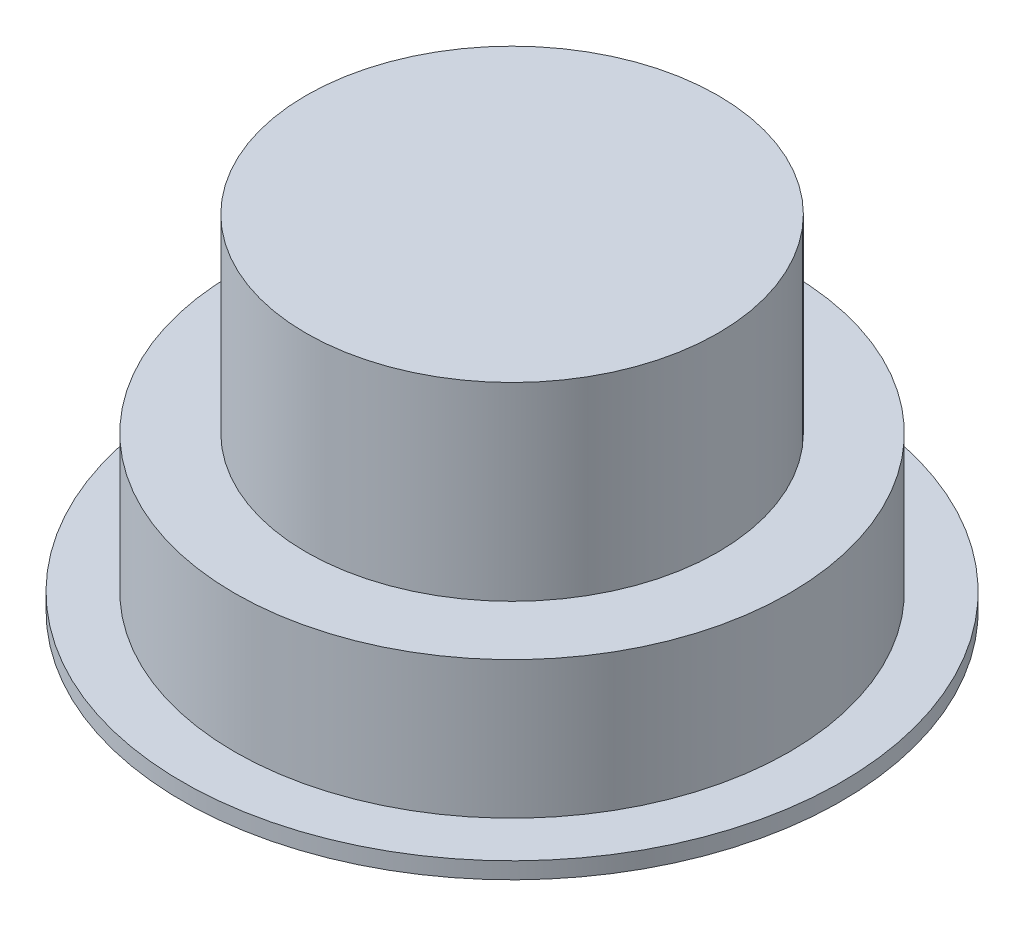
SolidWorks part; units mm, degrees
ref_plane "Plan de face" through (0, 0, 0) normal (0, 0, 1) x (1, 0, 0)
ref_plane "Plan de dessus" through (0, 0, 0) normal (0, 1, 0) x (1, 0, 0)
ref_plane "Plan de droite" through (0, 0, 0) normal (1, 0, 0) x (0, 0, -1)
sketch "Esquisse1" plane through (0, 0, 0) normal (0, 1, 0) x (1, 0, 0)
  circle A0 centre (0, 0) radius 7.5
  dimension "D1" = 15
extrude "Boss.-Extru.1" add sketch "Esquisse1" along normal blind 10.5
sketch "Esquisse2" plane through (0, 0, 0) normal (0, -1, 0) x (1, 0, 0)
  circle A0 centre (0, 0) radius 10.1
  dimension "D1" = 20.2
extrude "Boss.-Extru.2" add sketch "Esquisse2" along normal blind 2 and the other way blind 3.6
sketch "Esquisse3" plane through (0, -2, 0) normal (0, -1, 0) x (1, 0, 0)
  circle A0 centre (0, 0) radius 4.75
  dimension "D1" = 9.5
extrude "Enlèv. mat.-Extru.2" cut sketch "Esquisse3" against normal blind 7
sketch "Esquisse4" plane through (0, 5, 0) normal (0, -1, 0) x (1, 0, 0)
  circle A0 centre (0, 0) radius 2.9
  dimension "D1" = 5.8
extrude "Boss.-Extru.3" add sketch "Esquisse4" along normal blind 6
chamfer "Chanfrein1" distance 3.75 distance2 7.5 1 edges at (0, -2, -4.75) first distance on face at (0, -2, -4.75)
sketch "Esquisse11" plane through (0, -1, 0) normal (0, -1, 0) x (1, 0, 0)
  circle A0 centre (0, 0) radius 1.25
  dimension "D1" = 2.5
extrude "Enlèv. mat.-Extru.4" cut sketch "Esquisse11" against normal blind 7.5
sketch "Esquisse29" plane through (0, -2, 0) normal (0, -1, 0) x (1, 0, 0)
  circle A0 centre (0, 0) radius 10.1
  circle A1 centre (0, 0) radius 12
  dimension "D1" = 24
extrude "Boss.-Extru.11" add sketch "Esquisse29" against normal blind 0.6
fillet "Congé1" radius 2 1 edges at (0, -1, -1.25)
